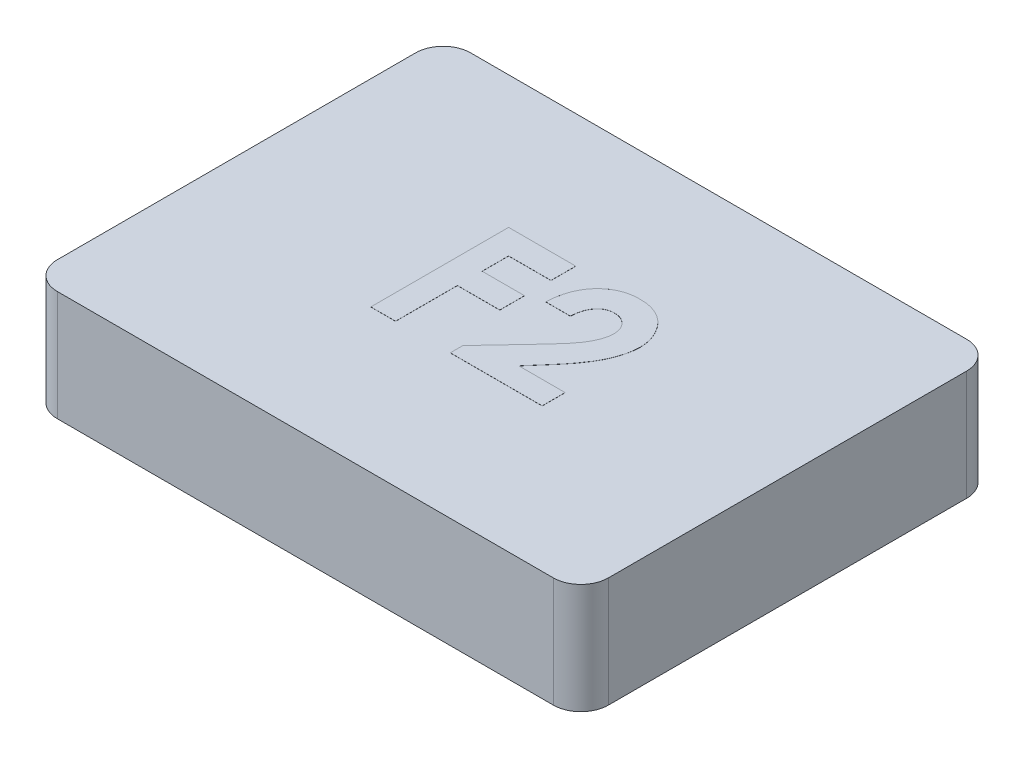
SolidWorks part; units mm, degrees
ref_plane "Front Plane" through (0, 0, 0) normal (0, 0, 1) x (1, 0, 0)
ref_plane "Top Plane" through (0, 0, 0) normal (0, 1, 0) x (1, 0, 0)
ref_plane "Right Plane" through (0, 0, 0) normal (1, 0, 0) x (0, 0, -1)
sketch "Sketch1" plane through (0, 0, 0) normal (0, 1, 0) x (1, 0, 0)
  line L0 (0, 0) -> (12.7, 0)
  line L1 (12.7, 0) -> (12.7, 9.525)
  line L2 (12.7, 9.525) -> (0, 9.525)
  line L3 (0, 9.525) -> (0, 0)
  dimension "D1" = 12.7
  dimension "D2" = 9.525
extrude "Boss-Extrude1" add sketch "Sketch1" along normal blind 2.54
fillet "Fillet1" radius 0.635 4 edges at (0, 1.27, -9.525) (12.7, 1.27, -9.525) (12.7, 1.27, 0) (0, 1.27, 0)
shell "Shell1" thickness 0.635 removed face at (6.35, 0, -4.7625)
sketch "Sketch2" plane through (0, 1.905, 0) normal (0, -1, 0) x (-1, 0, 0)
  line L0 (-0.635, 4.7625) -> (-12.065, 4.7625) construction
  line L1 (-0.635, 8.89) -> (-0.635, 0.635) construction
  line L2 (-12.065, 0.635) -> (-12.065, 8.89) construction
  line L3 (-6.35, 0.635) -> (-6.35, 8.89) construction
  line L4 (-0.635, 0.635) -> (-12.065, 0.635) construction
  line L5 (-12.065, 8.89) -> (-0.635, 8.89) construction
  circle A0 centre (-6.35, 4.7625) radius 2.54
  dimension "D1" = 5.08
extrude "Boss-Extrude2" add sketch "Sketch2" along normal up to surface (1.905 mm away) up to face at (6.35, 0, -4.7625)
sketch "Sketch3" plane through (0, 2.54, 0) normal (0, 1, 0) x (1, 0, 0)
  line L0 (0.635, 0) -> (12.065, 0) construction
  line L1 (0, 8.89) -> (0, 0.635) construction
  text T0 "<b>F2</b>"
  dimension "D1" = 3.302
  dimension "D2" = 4.191
extrude "Boss-Extrude3" add sketch "Sketch3" along normal blind 0.0025
